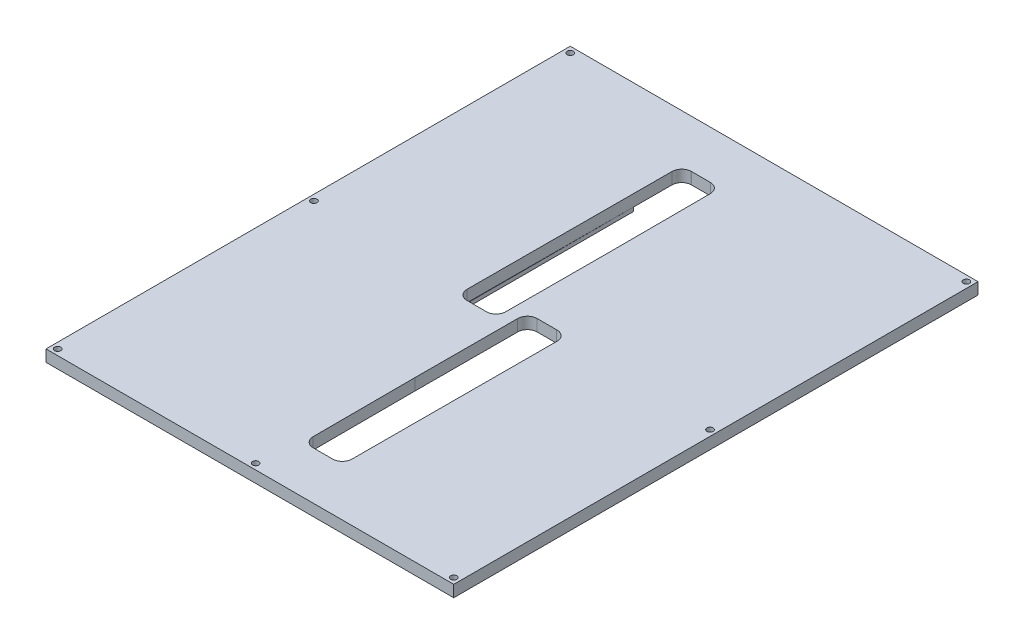
SolidWorks part; units mm, degrees
ref_plane "Front Plane" through (0, 0, 0) normal (0, 0, 1) x (1, 0, 0)
ref_plane "Top Plane" through (0, 0, 0) normal (0, 1, 0) x (1, 0, 0)
ref_plane "Right Plane" through (0, 0, 0) normal (1, 0, 0) x (0, 0, -1)
sketch "Sketch1" plane through (0, 0, 0) normal (0, 1, 0) x (1, 0, 0)
  line L0 (-23.9329, 105.348) -> (-24.1829, 0) construction
  line L1 (-24.1829, 0) -> (0, 0) construction
  line L2 (-17.9329, 105.348) -> (-18.1829, 0) construction
  line L3 (-12.9329, 105.3361) -> (-13.1829, -0.0119)
  line L8 (-22.9328, 105.3598) -> (-23.1828, 0.0119)
  line L10 (-105, -135) -> (105, -135)
  line L11 (23.9329, 105.348) -> (24.1829, 0) construction
  line L12 (18.9329, 105.3361) -> (19.1829, -0.0119) construction
  line L13 (28.9328, 105.3598) -> (29.1828, 0.0119) construction
  line L14 (17.9329, -105.3242) -> (18.1829, 0.0237) construction
  line L15 (12.9329, -105.3124) -> (13.1829, 0.0356)
  line L16 (22.9328, -105.3361) -> (23.1828, 0.0119)
  line L17 (-105, -135) -> (-105, 135)
  line L26 (-105, 135) -> (105, 135)
  line L27 (105, -135) -> (105, 135)
  line L28 (-105, -135) -> (105, 135) construction
  line L29 (-105, 135) -> (105, -135) construction
  arc A0 (-12.9329, 105.3361) -> (-22.9328, 105.3598) centre (-17.9329, 105.348) ccw
  arc A1 (-23.1828, 0.0119) -> (-13.1829, -0.0119) centre (-18.1829, 0) ccw
  arc A2 (18.9329, 105.3361) -> (28.9328, 105.3598) centre (23.9329, 105.348) cw construction
  arc A3 (29.1828, 0.0119) -> (19.1829, -0.0119) centre (24.1829, 0) cw construction
  arc A4 (12.9329, -105.3124) -> (22.9328, -105.3361) centre (17.9329, -105.3242) ccw
  arc A5 (23.1828, 0.0119) -> (13.1829, 0.0356) centre (18.1829, 0.0237) ccw
  point P7 (-18.0579, 52.674)
  point P18 (24.0579, 52.674)
  point P25 (18.0579, -52.6502)
  dimension "D1" = 270
  dimension "D2" = 210
extrude "Boss-Extrude1" add sketch "Sketch1" along normal blind 6
sketch "Sketch2" plane through (0, 6, 0) normal (0, 1, 0) x (-1, 0, 0)
  line L0 (41.4329, -85.6479) -> (41.4329, 97) construction
  line L1 (31.4329, -85.6479) -> (41.4329, -85.6479)
  line L2 (31.4329, -85.6479) -> (31.4329, 97)
  line L3 (31.4329, 97) -> (41.4329, 97)
  line L4 (41.4329, -85.6479) -> (41.4329, 97)
  line L5 (25.9329, 97) -> (15.9329, 97) construction
  line L6 (25.9329, -85.6479) -> (22.9796, -85.6479)
  line L7 (25.9329, -85.6479) -> (25.9329, 97)
  line L8 (25.9329, 97) -> (22.9796, 97)
  line L9 (22.9796, -85.6479) -> (22.9796, 97)
  line L11 (22.9328, -105.3598) -> (23.1828, -0.0119) construction
extrude "Boss-Extrude2" add sketch "Sketch2" against normal blind 2 from surface starting at face at (0, 0, 0)
mirror "Mirror1" about plane through (0, 0, 0) normal (1, 0, 0) of "Boss-Extrude2"
sketch "Sketch3" plane through (0, 0, 0) normal (0, -1, 0) x (1, 0, 0)
  line L4 (102, -132) -> (102, 132) construction
  line L5 (102, 132) -> (-102, 132) construction
  line L6 (-102, 132) -> (-102, -132) construction
  line L7 (-102, -132) -> (102, -132) construction
  line L12 (105, -135) -> (105, 135)
  line L13 (105, 135) -> (-105, 135)
  line L14 (-105, 135) -> (-105, -135)
  line L15 (-105, -135) -> (105, -135)
  line L16 (105, -135) -> (105, 135) construction
  line L17 (105, 135) -> (-105, 135) construction
  line L18 (-105, 135) -> (-105, -135) construction
  line L19 (-105, -135) -> (105, -135) construction
  circle A8 centre (-102, 132) radius 1.6
  circle A9 centre (0, 132) radius 1.6
  circle A10 centre (102, 132) radius 1.6
  circle A11 centre (-102, 0) radius 1.6
  circle A12 centre (-102, -132) radius 1.6
  circle A13 centre (102, -132) radius 1.6
  circle A14 centre (102, 0) radius 1.6
  dimension "D3" = 3.2
  dimension "D2" = 3
  dimension "D1" = 0
extrude "Cut-Extrude1" cut sketch "Sketch3" against normal blind 30
sketch "Sketch4" plane through (0, 0, 0) normal (0, -1, 0) x (1, 0, 0)
  line L0 (-8.1829, 5) -> (-18.1829, 5)
  line L1 (-3.1829, 0.0119) -> (-3.0578, -52.674)
  line L3 (-18.1829, 5) -> (-18.0519, -52.674)
  line L4 (-18.0519, -52.674) -> (-3.0578, -52.674) construction
  line L5 (-18.1829, -110.3479) -> (-18.0519, -52.674)
  line L6 (-3.1829, -105.3598) -> (-3.0578, -52.674)
  line L7 (-8.1829, -110.3479) -> (-18.1829, -110.3479)
  arc A0 (-13.1829, 0.0119) -> (-22.9796, 1.411) centre (-18.1829, 0) ccw construction
  arc A3 (-3.1829, 0.0119) -> (-8.1829, 5) centre (-8.1829, 0) ccw
  arc A4 (-3.1829, -105.3598) -> (-8.1829, -110.3479) centre (-8.1829, -105.3479) cw
extrude "Cut-Extrude2" cut sketch "Sketch4" against normal blind 10
sketch "Sketch5" plane through (0, 0, 0) normal (0, -1, 0) x (1, 0, 0)
  line L8 (17.7901, 52.6502) -> (2.796, 52.6502) construction
  line L9 (7.921, -5.0237) -> (17.921, -5.0237)
  line L10 (2.921, -0.0356) -> (2.796, 52.6502)
  line L11 (17.921, -5.0237) -> (17.7901, 52.6502)
  line L12 (17.921, 110.3242) -> (17.7901, 52.6502)
  line L13 (2.921, 105.3361) -> (2.796, 52.6502)
  line L14 (7.921, 110.3242) -> (17.921, 110.3242)
  arc A2 (2.921, -0.0356) -> (7.921, -5.0237) centre (7.921, -0.0237) ccw
  arc A3 (2.921, 105.3361) -> (7.921, 110.3242) centre (7.921, 105.3242) cw
  arc A4 (22.9328, 105.3361) -> (12.9329, 105.3124) centre (17.9329, 105.3242) ccw construction
  point P0 (17.921, 110.3242)
extrude "Cut-Extrude3" cut sketch "Sketch5" against normal blind 10
